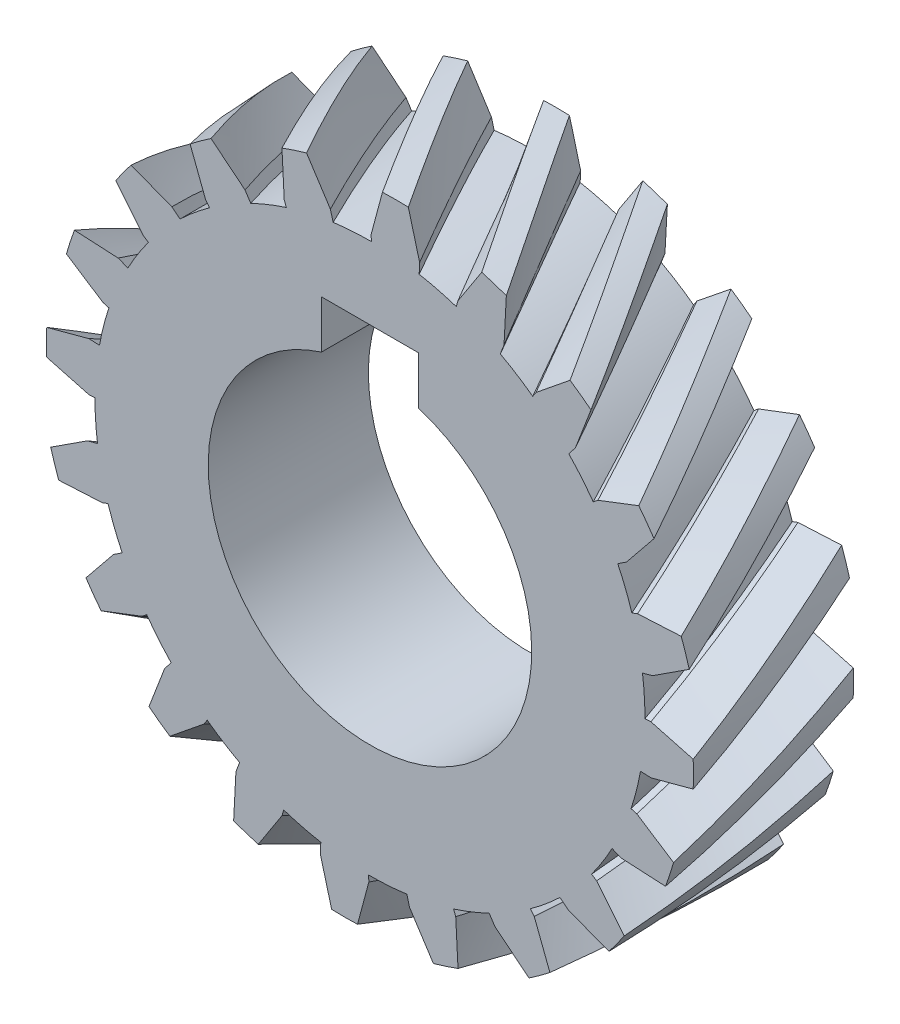
SolidWorks part; units mm, degrees
ref_plane "Front Plane" through (0, 0, 0) normal (0, 0, 1) x (1, 0, 0)
ref_plane "Top Plane" through (0, 0, 0) normal (0, 1, 0) x (1, 0, 0)
ref_plane "Right Plane" through (0, 0, 0) normal (1, 0, 0) x (0, 0, -1)
sketch "Sketch1" plane through (0, 0, 0) normal (0, 0, 1) x (1, 0, 0)
  line L0 (3.5, 1.9365) -> (3.5, -1.9365) construction
  line L1 (0, 0) -> (0, 4) construction
  line L2 (0, 9) -> (0, 10) construction
  line L3 (0, 4) -> (0, 9) construction
  line L4 (0.4, 9.992) -> (0.75, 8.6858)
  line L5 (0.75, 8.6858) -> (0.75, 8.4668)
  line L6 (-0.75, 8.6858) -> (-0.75, 8.4668)
  line L7 (-0.4, 9.992) -> (-0.75, 8.6858)
  line L8 (2.4831, 8.357) -> (2.439, 8.1426)
  line L9 (1.0138, 8.659) -> (0.9697, 8.4445)
  line L10 (1.6196, 9.868) -> (1.0138, 8.659)
  line L11 (2.4032, 9.7069) -> (2.4831, 8.357)
  line L12 (4.1145, 7.6861) -> (4.0282, 7.4849)
  line L13 (2.7361, 8.2776) -> (2.6497, 8.0764)
  line L14 (3.5728, 9.34) -> (2.7361, 8.2776)
  line L15 (4.308, 9.0245) -> (4.1145, 7.6861)
  line L16 (5.5775, 6.7005) -> (5.4524, 6.5208)
  line L17 (4.3463, 7.5574) -> (4.2213, 7.3777)
  line L18 (5.3798, 8.4296) -> (4.3463, 7.5574)
  line L19 (6.0364, 7.9726) -> (5.5775, 6.7005)
  line L20 (6.8121, 5.4406) -> (6.6534, 5.2898)
  line L21 (5.7787, 6.5278) -> (5.62, 6.377)
  line L22 (6.9665, 7.1741) -> (5.7787, 6.5278)
  line L23 (7.5177, 6.5942) -> (6.8121, 5.4406)
  line L24 (7.7679, 3.958) -> (7.5821, 3.8422)
  line L25 (6.9744, 5.2309) -> (6.7886, 5.1151)
  line L26 (8.2681, 5.6249) -> (6.9744, 5.2309)
  line L27 (8.6912, 4.9459) -> (7.7679, 3.958)
  line L28 (8.4056, 2.3133) -> (8.2003, 2.2373)
  line L29 (7.8846, 3.7199) -> (7.6793, 3.6439)
  line L30 (9.2311, 3.8454) -> (7.8846, 3.7199)
  line L31 (9.5089, 3.0952) -> (8.4056, 2.3133)
  line L32 (8.6992, 0.5739) -> (8.4828, 0.5408)
  line L33 (8.472, 2.0566) -> (8.2556, 2.0235)
  line L34 (9.8162, 1.9085) -> (8.472, 2.0566)
  line L35 (9.9373, 1.1177) -> (8.6992, 0.5739)
  line L36 (8.6366, -1.189) -> (8.418, -1.1779)
  line L37 (8.7126, 0.3091) -> (8.494, 0.3202)
  line L38 (9.9994, -0.1066) -> (8.7126, 0.3091)
  line L39 (9.9589, -0.9056) -> (8.6366, -1.189)
  line L40 (8.2205, -2.9032) -> (8.0086, -2.8483)
  line L41 (8.5965, -1.4511) -> (8.3846, -1.3962)
  line L42 (9.7733, -2.1173) -> (8.5965, -1.4511)
  line L43 (9.5728, -2.8918) -> (8.2205, -2.9032)
  line L44 (7.4678, -4.4985) -> (7.2713, -4.4021)
  line L45 (8.1284, -3.1518) -> (7.9319, -3.0554)
  line L46 (9.147, -4.0413) -> (8.1284, -3.1518)
  line L47 (8.7947, -4.7595) -> (7.4678, -4.4985)
  line L48 (6.4094, -5.9097) -> (6.2363, -5.7757)
  line L49 (7.3276, -4.7235) -> (7.1545, -4.5895)
  line L50 (8.1463, -5.7999) -> (7.3276, -4.7235)
  line L51 (7.6566, -6.4325) -> (6.4094, -5.9097)
  line L52 (5.0886, -7.0789) -> (4.946, -6.9128)
  line L53 (6.2267, -6.1019) -> (6.0841, -5.9358)
  line L54 (6.812, -7.321) -> (6.2267, -6.1019)
  line L55 (6.205, -7.8421) -> (5.0886, -7.0789)
  line L56 (3.5595, -7.9584) -> (3.4532, -7.7669)
  line L57 (4.871, -7.2304) -> (4.7647, -7.039)
  line L58 (5.1989, -8.5423) -> (4.871, -7.2304)
  line L59 (4.4994, -8.9306) -> (3.5595, -7.9584)
  line L60 (1.8846, -8.512) -> (1.8191, -8.3031)
  line L61 (3.3158, -8.0629) -> (3.2503, -7.854)
  line L62 (3.3729, -9.414) -> (3.3158, -8.0629)
  line L63 (2.6096, -9.6535) -> (1.8846, -8.512)
  line L64 (0.1326, -8.7171) -> (0.1104, -8.4993)
  line L65 (1.6249, -8.5653) -> (1.6027, -8.3475)
  line L66 (1.4088, -9.9003) -> (1.6249, -8.5653)
  line L67 (0.6129, -9.9812) -> (0.1326, -8.7171)
  line L68 (-1.6249, -8.5653) -> (-1.6027, -8.3475)
  line L69 (-0.1326, -8.7171) -> (-0.1104, -8.4993)
  line L70 (-0.6129, -9.9812) -> (-0.1326, -8.7171)
  line L71 (-1.4088, -9.9003) -> (-1.6249, -8.5653)
  line L72 (-3.3158, -8.0629) -> (-3.2503, -7.854)
  line L73 (-1.8846, -8.512) -> (-1.8191, -8.3031)
  line L74 (-2.6096, -9.6535) -> (-1.8846, -8.512)
  line L75 (-3.3729, -9.414) -> (-3.3158, -8.0629)
  line L76 (-4.871, -7.2304) -> (-4.7647, -7.039)
  line L77 (-3.5595, -7.9584) -> (-3.4532, -7.7669)
  line L78 (-4.4994, -8.9306) -> (-3.5595, -7.9584)
  line L79 (-5.1989, -8.5423) -> (-4.871, -7.2304)
  line L80 (-6.2267, -6.1019) -> (-6.0841, -5.9358)
  line L81 (-5.0886, -7.0789) -> (-4.946, -6.9128)
  line L82 (-6.205, -7.8421) -> (-5.0886, -7.0789)
  line L83 (-6.812, -7.321) -> (-6.2267, -6.1019)
  line L84 (-7.3276, -4.7235) -> (-7.1545, -4.5895)
  line L85 (-6.4094, -5.9097) -> (-6.2363, -5.7757)
  line L86 (-7.6566, -6.4325) -> (-6.4094, -5.9097)
  line L87 (-8.1463, -5.7999) -> (-7.3276, -4.7235)
  line L88 (-8.1284, -3.1518) -> (-7.9319, -3.0554)
  line L89 (-7.4678, -4.4985) -> (-7.2713, -4.4021)
  line L90 (-8.7947, -4.7595) -> (-7.4678, -4.4985)
  line L91 (-9.147, -4.0413) -> (-8.1284, -3.1518)
  line L92 (-8.5965, -1.4511) -> (-8.3846, -1.3962)
  line L93 (-8.2205, -2.9032) -> (-8.0086, -2.8483)
  line L94 (-9.5728, -2.8918) -> (-8.2205, -2.9032)
  line L95 (-9.7733, -2.1173) -> (-8.5965, -1.4511)
  line L96 (-8.7126, 0.3091) -> (-8.494, 0.3202)
  line L97 (-8.6366, -1.189) -> (-8.418, -1.1779)
  line L98 (-9.9589, -0.9056) -> (-8.6366, -1.189)
  line L99 (-9.9994, -0.1066) -> (-8.7126, 0.3091)
  line L100 (-8.472, 2.0566) -> (-8.2556, 2.0235)
  line L101 (-8.6992, 0.5739) -> (-8.4828, 0.5408)
  line L102 (-9.9373, 1.1177) -> (-8.6992, 0.5739)
  line L103 (-9.8162, 1.9085) -> (-8.472, 2.0566)
  line L104 (-7.8846, 3.7199) -> (-7.6793, 3.6439)
  line L105 (-8.4056, 2.3133) -> (-8.2003, 2.2373)
  line L106 (-9.5089, 3.0952) -> (-8.4056, 2.3133)
  line L107 (-9.2311, 3.8454) -> (-7.8846, 3.7199)
  line L108 (-6.9744, 5.2309) -> (-6.7886, 5.1151)
  line L109 (-7.7679, 3.958) -> (-7.5821, 3.8422)
  line L110 (-8.6912, 4.9459) -> (-7.7679, 3.958)
  line L111 (-8.2681, 5.6249) -> (-6.9744, 5.2309)
  line L112 (-5.7787, 6.5278) -> (-5.62, 6.377)
  line L113 (-6.8121, 5.4406) -> (-6.6534, 5.2898)
  line L114 (-7.5177, 6.5942) -> (-6.8121, 5.4406)
  line L115 (-6.9665, 7.1741) -> (-5.7787, 6.5278)
  line L116 (-4.3463, 7.5574) -> (-4.2213, 7.3777)
  line L117 (-5.5775, 6.7005) -> (-5.4524, 6.5208)
  line L118 (-6.0364, 7.9726) -> (-5.5775, 6.7005)
  line L119 (-5.3798, 8.4296) -> (-4.3463, 7.5574)
  line L120 (-2.7361, 8.2776) -> (-2.6497, 8.0764)
  line L121 (-4.1145, 7.6861) -> (-4.0282, 7.4849)
  line L122 (-4.308, 9.0245) -> (-4.1145, 7.6861)
  line L123 (-3.5728, 9.34) -> (-2.7361, 8.2776)
  line L124 (-1.0138, 8.659) -> (-0.9697, 8.4445)
  line L125 (-2.4831, 8.357) -> (-2.439, 8.1426)
  line L126 (-2.4032, 9.7069) -> (-2.4831, 8.357)
  line L127 (-1.6196, 9.868) -> (-1.0138, 8.659)
  arc A0 (3.5, 1.9365) -> (3.5, -1.9365) centre (0, 0) ccw construction
  arc A2 (0.4, 9.992) -> (-0.4, 9.992) centre (0, 0) ccw
  arc A3 (0.75, 8.4668) -> (-0.75, 8.4668) centre (0, 0) ccw
  circle A4 centre (0, 0) radius 8.5 construction
  arc A5 (2.439, 8.1426) -> (0.9697, 8.4445) centre (0, 0) ccw
  arc A6 (2.4032, 9.7069) -> (1.6196, 9.868) centre (0, 0) ccw
  arc A7 (4.0282, 7.4849) -> (2.6497, 8.0764) centre (0, 0) ccw
  arc A8 (4.308, 9.0245) -> (3.5728, 9.34) centre (0, 0) ccw
  arc A9 (5.4524, 6.5208) -> (4.2213, 7.3777) centre (0, 0) ccw
  arc A10 (6.0364, 7.9726) -> (5.3798, 8.4296) centre (0, 0) ccw
  arc A11 (6.6534, 5.2898) -> (5.62, 6.377) centre (0, 0) ccw
  arc A12 (7.5177, 6.5942) -> (6.9665, 7.1741) centre (0, 0) ccw
  arc A13 (7.5821, 3.8422) -> (6.7886, 5.1151) centre (0, 0) ccw
  arc A14 (8.6912, 4.9459) -> (8.2681, 5.6249) centre (0, 0) ccw
  arc A15 (8.2003, 2.2373) -> (7.6793, 3.6439) centre (0, 0) ccw
  arc A16 (9.5089, 3.0952) -> (9.2311, 3.8454) centre (0, 0) ccw
  arc A17 (8.4828, 0.5408) -> (8.2556, 2.0235) centre (0, 0) ccw
  arc A18 (9.9373, 1.1177) -> (9.8162, 1.9085) centre (0, 0) ccw
  arc A19 (8.418, -1.1779) -> (8.494, 0.3202) centre (0, 0) ccw
  arc A20 (9.9589, -0.9056) -> (9.9994, -0.1066) centre (0, 0) ccw
  arc A21 (8.0086, -2.8483) -> (8.3846, -1.3962) centre (0, 0) ccw
  arc A22 (9.5728, -2.8918) -> (9.7733, -2.1173) centre (0, 0) ccw
  arc A23 (7.2713, -4.4021) -> (7.9319, -3.0554) centre (0, 0) ccw
  arc A24 (8.7947, -4.7595) -> (9.147, -4.0413) centre (0, 0) ccw
  arc A25 (6.2363, -5.7757) -> (7.1545, -4.5895) centre (0, 0) ccw
  arc A26 (7.6566, -6.4325) -> (8.1463, -5.7999) centre (0, 0) ccw
  arc A27 (4.946, -6.9128) -> (6.0841, -5.9358) centre (0, 0) ccw
  arc A28 (6.205, -7.8421) -> (6.812, -7.321) centre (0, 0) ccw
  arc A29 (3.4532, -7.7669) -> (4.7647, -7.039) centre (0, 0) ccw
  arc A30 (4.4994, -8.9306) -> (5.1989, -8.5423) centre (0, 0) ccw
  arc A31 (1.8191, -8.3031) -> (3.2503, -7.854) centre (0, 0) ccw
  arc A32 (2.6096, -9.6535) -> (3.3729, -9.414) centre (0, 0) ccw
  arc A33 (0.1104, -8.4993) -> (1.6027, -8.3475) centre (0, 0) ccw
  arc A34 (0.6129, -9.9812) -> (1.4088, -9.9003) centre (0, 0) ccw
  arc A35 (-1.6027, -8.3475) -> (-0.1104, -8.4993) centre (0, 0) ccw
  arc A36 (-1.4088, -9.9003) -> (-0.6129, -9.9812) centre (0, 0) ccw
  arc A37 (-3.2503, -7.854) -> (-1.8191, -8.3031) centre (0, 0) ccw
  arc A38 (-3.3729, -9.414) -> (-2.6096, -9.6535) centre (0, 0) ccw
  arc A39 (-4.7647, -7.039) -> (-3.4532, -7.7669) centre (0, 0) ccw
  arc A40 (-5.1989, -8.5423) -> (-4.4994, -8.9306) centre (0, 0) ccw
  arc A41 (-6.0841, -5.9358) -> (-4.946, -6.9128) centre (0, 0) ccw
  arc A42 (-6.812, -7.321) -> (-6.205, -7.8421) centre (0, 0) ccw
  arc A43 (-7.1545, -4.5895) -> (-6.2363, -5.7757) centre (0, 0) ccw
  arc A44 (-8.1463, -5.7999) -> (-7.6566, -6.4325) centre (0, 0) ccw
  arc A45 (-7.9319, -3.0554) -> (-7.2713, -4.4021) centre (0, 0) ccw
  arc A46 (-9.147, -4.0413) -> (-8.7947, -4.7595) centre (0, 0) ccw
  arc A47 (-8.3846, -1.3962) -> (-8.0086, -2.8483) centre (0, 0) ccw
  arc A48 (-9.7733, -2.1173) -> (-9.5728, -2.8918) centre (0, 0) ccw
  arc A49 (-8.494, 0.3202) -> (-8.418, -1.1779) centre (0, 0) ccw
  arc A50 (-9.9994, -0.1066) -> (-9.9589, -0.9056) centre (0, 0) ccw
  arc A51 (-8.2556, 2.0235) -> (-8.4828, 0.5408) centre (0, 0) ccw
  arc A52 (-9.8162, 1.9085) -> (-9.9373, 1.1177) centre (0, 0) ccw
  arc A53 (-7.6793, 3.6439) -> (-8.2003, 2.2373) centre (0, 0) ccw
  arc A54 (-9.2311, 3.8454) -> (-9.5089, 3.0952) centre (0, 0) ccw
  arc A55 (-6.7886, 5.1151) -> (-7.5821, 3.8422) centre (0, 0) ccw
  arc A56 (-8.2681, 5.6249) -> (-8.6912, 4.9459) centre (0, 0) ccw
  arc A57 (-5.62, 6.377) -> (-6.6534, 5.2898) centre (0, 0) ccw
  arc A58 (-6.9665, 7.1741) -> (-7.5177, 6.5942) centre (0, 0) ccw
  arc A59 (-4.2213, 7.3777) -> (-5.4524, 6.5208) centre (0, 0) ccw
  arc A60 (-5.3798, 8.4296) -> (-6.0364, 7.9726) centre (0, 0) ccw
  arc A61 (-2.6497, 8.0764) -> (-4.0282, 7.4849) centre (0, 0) ccw
  arc A62 (-3.5728, 9.34) -> (-4.308, 9.0245) centre (0, 0) ccw
  arc A63 (-0.9697, 8.4445) -> (-2.439, 8.1426) centre (0, 0) ccw
  arc A64 (-1.6196, 9.868) -> (-2.4032, 9.7069) centre (0, 0) ccw
  point P197 (0, 0)
  dimension "D1" = 8
  dimension "D3" = 31
  dimension "D9" = 8.5
  dimension "D10" = 10
  dimension "D2" = 3.5
  dimension "D4" = 1
  dimension "D5" = 15
  dimension "D6" = 0
  dimension "D7" = 0.4
  dimension "D8" = 1.5
ref_plane "Plane1" through (0, 0, 10) normal (0, 0, 1) x (1, 0, 0)
sketch "Sketch2" plane through (0, 0, 10) normal (0, 0, 1) x (1, 0, 0)
  line L2 (0, 9) -> (0, 10) construction
  line L3 (0, 4) -> (0, 9) construction
  line L4 (0.4, 9.992) -> (0.75, 8.6858)
  line L5 (0.75, 8.6858) -> (0.7279, 8.2178)
  line L6 (-0.75, 8.6858) -> (-0.7279, 8.2178)
  line L7 (-0.4, 9.992) -> (-0.75, 8.6858)
  arc A2 (0.4, 9.992) -> (-0.4, 9.992) centre (0, 0) ccw
  arc A3 (0.7279, 8.2178) -> (-0.7279, 8.2178) centre (0, 0) ccw
  dimension "D1" = 8.25
  dimension "D2" = 10
  dimension "D7" = 0.4
sketch "Sketch4" plane through (0, 0, 0) normal (0, 1, 0) x (1, 0, 0)
  line L0 (0, 0) -> (0, -6.0071) construction
sketch "Sketch5" plane through (0, 0, 0) normal (0, 0, 1) x (1, 0, 0)
  circle A0 centre (-0.7852, 0) radius 8.5
  circle A4 centre (-0.7852, 0) radius 5
  dimension "D1" = 10
extrude "Boss-Extrude1" add sketch "Sketch5" along normal blind 10
sketch "Sketch6" plane through (0, 0, 10) normal (0, 0, 1) x (1, 0, 0)
  circle A1 centre (-0.7852, 0) radius 8.5
  circle A2 centre (-0.7852, 0) radius 8.5
  dimension "D1" = 0
curve "Helix/Spiral1" pitch 100 height 10 turns 0.1
sweep "Sweep1" add profiles "Sketch2" path "Helix/Spiral1"
pattern_circular "CirPattern1" count 20 over 360 about axis through (-0.7852, 0, 10) along (0, 0, -1) of "Sweep1"
sketch "Sketch8" plane through (0, 0, 0) normal (0, 0, -1) x (-1, 0, 0)
  circle A0 centre (0, 0) radius 21.0121
extrude "Cut-Extrude1" cut sketch "Sketch8" against normal mid plane 0.1
sketch "Sketch10" plane through (0, 0, 0.05) normal (0, 0, -1) x (-1, 0, 0)
  circle A0 centre (0, 0) radius 21.6793
extrude "Cut-Extrude2" cut sketch "Sketch10" against normal blind 5
sketch "Sketch11" plane through (0, 0, 5.05) normal (0, 0, -1) x (-1, 0, 0)
  line L0 (0.7852, 5) -> (0.7852, -5) construction
  line L2 (-0.7148, 6.25) -> (2.2852, 6.25)
  line L3 (-0.7148, 6.25) -> (-0.7148, 3.75)
  line L4 (-0.7148, 3.75) -> (2.2852, 3.75)
  line L5 (2.2852, 6.25) -> (2.2852, 3.75)
  line L6 (-0.7148, 6.25) -> (2.2852, 3.75) construction
  line L7 (-0.7148, 3.75) -> (2.2852, 6.25) construction
  circle A1 centre (0.7852, 0) radius 5 construction
  dimension "D1" = 2.5
  dimension "D2" = 3
extrude "Cut-Extrude4" cut sketch "Sketch11" against normal up to surface (4.95 mm away) up to face at (-0.7852, 0, 10)
